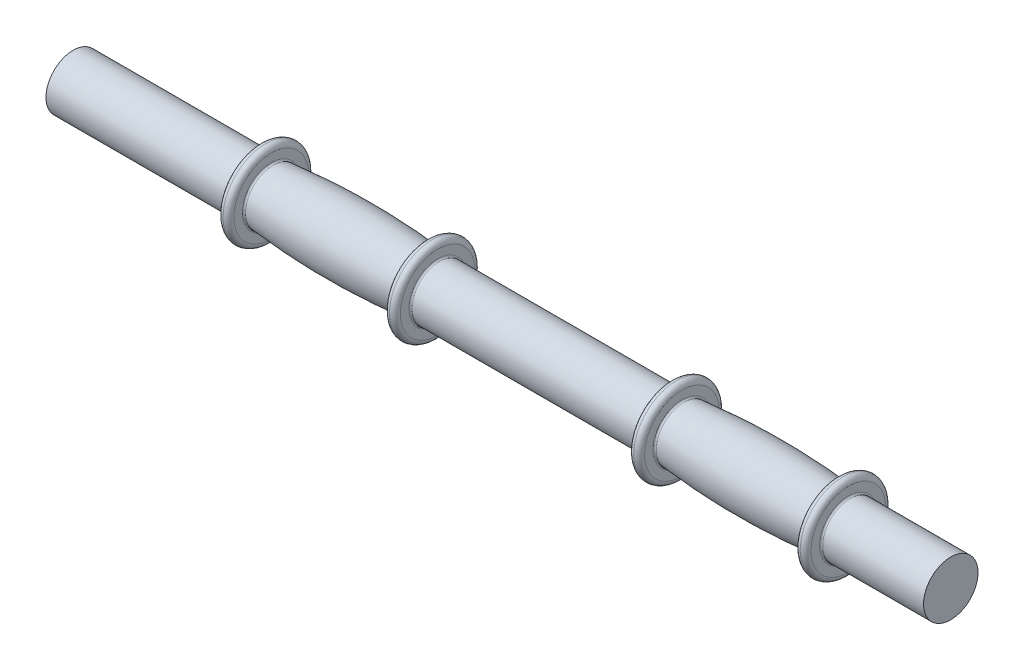
SolidWorks part; units mm, degrees
ref_plane "Front Plane" through (0, 0, 0) normal (0, 0, 1) x (1, 0, 0)
ref_plane "Top Plane" through (0, 0, 0) normal (0, 1, 0) x (1, 0, 0)
ref_plane "Right Plane" through (0, 0, 0) normal (1, 0, 0) x (0, 0, -1)
sketch "Sketch1" plane through (0, 0, 0) normal (0, 0, 1) x (1, 0, 0)
  line L0 (0, 0) -> (0, 17.5)
  line L1 (0, 17.5) -> (120.32, 17.5)
  line L2 (120.32, 17.5) -> (120.32, 27.5)
  line L3 (120.32, 27.5) -> (127.32, 27.5)
  line L4 (127.32, 27.5) -> (127.32, 17.5)
  line L5 (227.32, 17.5) -> (227.32, 27.5)
  line L6 (227.32, 27.5) -> (234.32, 27.5)
  line L7 (234.32, 27.5) -> (234.32, 17.5)
  line L8 (234.32, 17.5) -> (384.32, 17.5)
  line L9 (384.32, 17.5) -> (384.32, 27.5)
  line L10 (384.32, 27.5) -> (391.32, 27.5)
  line L11 (391.32, 27.5) -> (391.32, 17.5)
  line L12 (491.32, 17.5) -> (491.32, 27.5)
  line L13 (491.32, 27.5) -> (498.32, 27.5)
  line L14 (498.32, 27.5) -> (498.32, 17.5)
  line L15 (498.32, 17.5) -> (564.12, 17.5)
  line L16 (564.12, 17.5) -> (564.12, 0)
  line L17 (564.12, 0) -> (0, 0)
  line L18 (177.32, 0) -> (177.32, 140.5293) construction
  line L19 (441.32, 0) -> (441.32, 140.5293) construction
  spline S0 degree 2 poles (127.32, 17.5) (177.32, 22.5) (227.32, 17.5) knots 0 0 0 1 1 1
  spline S1 degree 2 poles (391.32, 17.5) (441.32, 22.5) (491.32, 17.5) knots 0 0 0 1 1 1
  dimension "D1" = 120.32
  dimension "D2" = 7
  dimension "D3" = 100
  dimension "D4" = 7
  dimension "D5" = 150
  dimension "D6" = 7
  dimension "D7" = 100
  dimension "D8" = 7
  dimension "D9" = 65.8
  dimension "D10" = 17.5
  dimension "D11" = 10
  dimension "D12" = 0
  dimension "D13" = 20
  dimension "D14" = 20
revolve "Revolve1" add sketch "Sketch1" angle 360 about L17
fillet "Fillet4" radius 3.5 8 edges at (498.32, 0, -27.5) (491.32, 0, -27.5) (391.32, 0, -27.5) (384.32, 0, -27.5) (234.32, 0, -27.5) (227.32, 0, -27.5) (127.32, 0, -27.5) (120.32, 0, -27.5)
fillet "Fillet5" radius 1 8 edges at (491.32, 0, -17.5) (498.32, 0, -17.5) (391.32, 0, -17.5) (384.32, 0, -17.5) (234.32, 0, -17.5) (227.32, 0, -17.5) (127.32, 0, -17.5) (120.32, 0, -17.5)
sketch "Sketch3" plane through (0, 0, 0) normal (-1, 0, 0) x (0, 0, 1)
  circle A0 centre (0, 0) radius 12.5
  dimension "D1" = 25
extrude "Boss-Extrude1" add sketch "Sketch3" against normal through all
extrude "Cut-Extrude2" cut sketch "Sketch3<2>" against normal offset from surface (559.12 mm away) 5 contours A0 up to face at (564.12, 0, -17.5)
sketch "Sketch3<2>" plane through (0, 0, 0) normal (-1, 0, 0) x (0, 0, 1) same geometry as "Sketch3"
sketch "Sketch2" plane through (0, 0, 0) normal (-1, 0, 0) x (0, 0, 1)
  circle A0 centre (0, 0) radius 12.5
  dimension "D1" = 25
